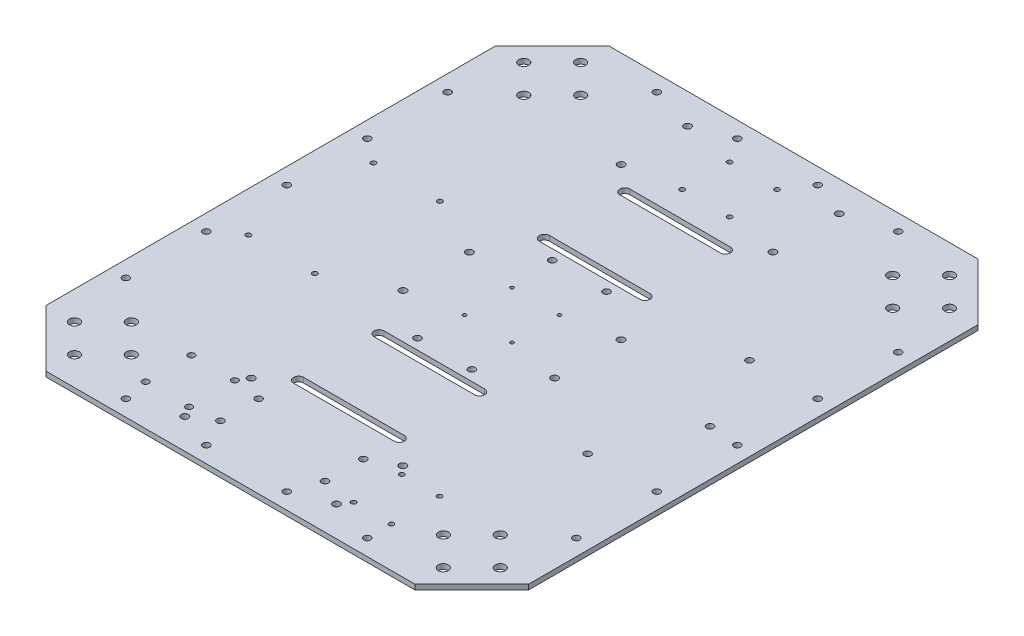
SolidWorks part; units mm, degrees
ref_plane "Front Plane" through (0, 0, 0) normal (0, 0, 1) x (1, 0, 0)
ref_plane "Top Plane" through (0, 0, 0) normal (0, 1, 0) x (1, 0, 0)
ref_plane "Right Plane" through (0, 0, 0) normal (1, 0, 0) x (0, 0, -1)
sketch "Sketch1" plane through (0, 0, 0) normal (0, 1, 0) x (1, 0, 0)
  line L0 (-121.2861, 87.138) -> (-85.365, 123.059)
  line L1 (-121.2861, 123.059) -> (183.5139, 123.059)
  line L2 (-121.2861, 123.059) -> (-121.2861, -232.541)
  line L3 (-121.2861, -232.541) -> (183.5139, -232.541)
  line L4 (183.5139, 123.059) -> (183.5139, -232.541)
  line L5 (31.1139, 95.069) -> (31.1139, -294.9418) construction
  line L6 (-146.0448, -54.741) -> (218.038, -54.741) construction
  line L7 (183.5139, 87.138) -> (147.5929, 123.059)
  line L8 (183.5139, -196.62) -> (147.5929, -232.541)
  line L9 (-121.2861, -196.62) -> (-85.365, -232.541)
  circle A0 centre (-16.7651, 104.009) radius 2.2225
  circle A1 centre (78.9929, 104.009) radius 2.2225
  circle A2 centre (-16.7651, 62.099) radius 2.2225
  circle A3 centre (78.9929, 62.099) radius 2.2225
  circle A4 centre (-16.7651, -171.581) radius 2.2225
  circle A5 centre (78.9929, -171.581) radius 2.2225
  circle A6 centre (78.9929, -213.491) radius 2.2225
  circle A7 centre (-16.7651, -213.491) radius 2.2225
  circle A8 centre (-16.7651, -33.786) radius 2.2225
  circle A9 centre (78.9929, -33.786) radius 2.2225
  circle A10 centre (78.9929, -75.696) radius 2.2225
  circle A11 centre (-16.7651, -75.696) radius 2.2225
  point P8 (31.1139, 123.059)
  point P11 (-121.2861, -54.741)
  dimension "D6" = 95.758
  dimension "D13" = 4.445
  dimension "D1" = 304.8
  dimension "D2" = 355.6
  dimension "D3" = 45
  dimension "D4" = 50.8
  dimension "D5" = 41.91
  dimension "D7" = 104.521
  dimension "D8" = 19.05
  dimension "D9" = 41.91
  dimension "D10" = 20.955
  dimension "D11" = 95.758
  dimension "D12" = 47.879
extrude "Boss-Extrude1" add sketch "Sketch1" along normal blind 3.175 contours L2 L9 L3 L8 L4 L7 L1 L0 region at (31.1139, 0, 54.741)
sketch "Sketch2" plane through (0, 3.175, 0) normal (0, 1, 0) x (1, 0, 0)
  line L0 (31.1139, 123.059) -> (31.1139, -287.8465) construction
  line L1 (-85.365, 123.059) -> (147.5929, 123.059) construction
  line L2 (183.5139, -54.741) -> (-158.2106, -54.741) construction
  line L3 (183.5139, 87.138) -> (183.5139, -196.62) construction
  circle A0 centre (13.8419, -12.069) radius 2.159
  circle A1 centre (48.1319, -12.069) radius 2.159
  circle A2 centre (13.8419, -97.159) radius 2.159
  circle A3 centre (48.1319, -97.159) radius 2.159
  dimension "D5" = 4.318
  dimension "D6" = 4.318
  dimension "D7" = 4.318
  dimension "D8" = 4.318
  dimension "D1" = 17.272
  dimension "D2" = 34.29
  dimension "D3" = 85.09
  dimension "D4" = 42.672
extrude "Cut-Extrude1" cut sketch "Sketch2" against normal through all
sketch "Sketch4" plane through (0, 3.175, 0) normal (0, 1, 0) x (1, 0, 0)
  line L0 (-0.6361, 48.256) -> (62.8639, 48.256) construction
  line L1 (-0.6361, 51.431) -> (62.8639, 51.431)
  line L2 (-0.6361, 45.081) -> (62.8639, 45.081)
  line L3 (-0.6361, -2.544) -> (62.8639, -2.544) construction
  line L4 (-0.6361, 0.631) -> (62.8639, 0.631)
  line L5 (-0.6361, -5.719) -> (62.8639, -5.719)
  line L6 (31.1139, 123.059) -> (31.1139, -75.2432) construction
  line L7 (-85.365, 123.059) -> (147.5929, 123.059) construction
  line L8 (-121.2861, -54.741) -> (257.7387, -54.741) construction
  line L9 (-121.2861, 87.138) -> (-121.2861, -196.62) construction
  line L10 (31.1139, -232.541) -> (31.1139, -34.2388) construction
  line L11 (-0.6361, -106.938) -> (62.8639, -106.938) construction
  line L12 (-0.6361, -110.113) -> (62.8639, -110.113)
  line L13 (-0.6361, -103.763) -> (62.8639, -103.763)
  line L14 (-0.6361, -157.738) -> (62.8639, -157.738) construction
  line L15 (-0.6361, -160.913) -> (62.8639, -160.913)
  line L16 (-0.6361, -154.563) -> (62.8639, -154.563)
  arc A0 (-0.6361, 51.431) -> (-0.6361, 45.081) centre (-0.6361, 48.256) ccw
  arc A1 (62.8639, 45.081) -> (62.8639, 51.431) centre (62.8639, 48.256) ccw
  arc A2 (-0.6361, 0.631) -> (-0.6361, -5.719) centre (-0.6361, -2.544) ccw
  arc A3 (62.8639, -5.719) -> (62.8639, 0.631) centre (62.8639, -2.544) ccw
  circle A4 centre (48.1319, -12.069) radius 2.159 construction
  arc A5 (-0.6361, -110.113) -> (-0.6361, -103.763) centre (-0.6361, -106.938) cw
  arc A6 (62.8639, -103.763) -> (62.8639, -110.113) centre (62.8639, -106.938) cw
  arc A7 (-0.6361, -160.913) -> (-0.6361, -154.563) centre (-0.6361, -157.738) cw
  arc A8 (62.8639, -154.563) -> (62.8639, -160.913) centre (62.8639, -157.738) cw
  point P2 (31.1139, 48.256)
  point P7 (31.1139, -2.544)
  point P28 (31.1139, -106.938)
  point P35 (31.1139, -157.738)
  dimension "D1" = 63.5
  dimension "D2" = 63.5
  dimension "D3" = 6.35
  dimension "D4" = 6.35
  dimension "D5" = 44.45
  dimension "D6" = 6.35
extrude "Cut-Extrude2" cut sketch "Sketch4" against normal through all
sketch "Sketch7" plane through (0, 3.175, 0) normal (0, 1, 0) x (1, 0, 0)
  line L0 (31.1139, 123.059) -> (31.1139, -19.2461) construction
  line L3 (-85.365, 123.059) -> (147.5929, 123.059) construction
  circle A0 centre (16.1279, 67.687) radius 1.524
  circle A1 centre (46.0999, 67.687) radius 1.524
  circle A2 centre (16.1279, 97.659) radius 1.524
  circle A3 centre (46.0999, 97.659) radius 1.524
  dimension "D1" = 3.048
  dimension "D2" = 3.048
  dimension "D4" = 14.986
  dimension "D3" = 29.972
  dimension "D5" = 25.4
extrude "Cut-Extrude3" cut sketch "Sketch7" against normal through all
sketch "Sketch8" plane through (0, 3.175, 0) normal (0, 1, 0) x (1, 0, 0)
  line L0 (-85.365, -232.541) -> (147.5929, -232.541) construction
  line L1 (183.5139, 87.138) -> (183.5139, -196.62) construction
  circle A0 centre (83.4379, -207.141) radius 1.524
  circle A1 centre (83.4379, -176.661) radius 1.524
  circle A2 centre (107.3139, -207.141) radius 1.524
  circle A3 centre (107.3139, -176.661) radius 1.524
  dimension "D1" = 3.048
  dimension "D2" = 30.48
  dimension "D3" = 23.876
  dimension "D4" = 25.4
  dimension "D5" = 76.2
extrude "Cut-Extrude4" cut sketch "Sketch8" against normal through all and the other way through all
sketch "Sketch9" plane through (0, 0, 0) normal (0, -1, 0) x (-1, 0, 0)
  line L0 (85.365, -232.541) -> (-147.5929, -232.541) construction
  line L1 (121.2861, 87.138) -> (121.2861, -196.62) construction
  circle A0 centre (48.1341, -206.887) radius 2.032
  circle A1 centre (20.7021, -206.887) radius 2.032
  circle A2 centre (48.1341, -177.931) radius 2.032
  circle A3 centre (20.7021, -177.931) radius 2.032
  dimension "D1" = 4.064
  dimension "D2" = 27.432
  dimension "D3" = 28.956
  dimension "D4" = 25.654
  dimension "D5" = 73.152
extrude "Cut-Extrude5" cut sketch "Sketch9" against normal through all
sketch "Sketch10" plane through (0, 0, 0) normal (0, -1, 0) x (1, 0, 0)
  line L0 (-85.365, 232.541) -> (147.5929, 232.541) construction
  line L1 (183.5139, -87.138) -> (183.5139, 196.62) construction
  circle A0 centre (-3.1761, 204.601) radius 2.159
  circle A1 centre (62.8639, 204.601) radius 2.159
  circle A2 centre (-3.1761, 180.471) radius 2.159
  circle A3 centre (62.8639, 180.471) radius 2.159
  dimension "D1" = 4.318
  dimension "D2" = 66.04
  dimension "D4" = 27.94
  dimension "D6" = 4.318
  dimension "D7" = 4.318
  dimension "D8" = 4.318
  dimension "D3" = 24.13
  dimension "D5" = 120.65
extrude "Cut-Extrude6" cut sketch "Sketch10" against normal through all
sketch "Sketch12" plane through (0, 0, 0) normal (0, -1, 0) x (1, 0, 0)
  line L0 (-121.2861, 54.741) -> (204.2138, 54.741) construction
  line L1 (-121.2861, -87.138) -> (-121.2861, 196.62) construction
  circle A0 centre (-95.8861, 94.216) radius 1.575
  circle A1 centre (-95.8861, 15.266) radius 1.575
  circle A2 centre (-53.9361, 15.266) radius 1.575
  circle A3 centre (-53.9361, 94.216) radius 1.575
  dimension "D1" = 3.15
  dimension "D2" = 3.15
  dimension "D3" = 3.15
  dimension "D4" = 3.15
  dimension "D5" = 78.95
  dimension "D6" = 39.475
  dimension "D7" = 41.95
  dimension "D8" = 25.4
extrude "Cut-Extrude7" cut sketch "Sketch12" against normal through all
sketch "Sketch13" plane through (0, 0, 0) normal (0, -1, 0) x (1, 0, 0)
  line L0 (31.1139, -123.059) -> (31.1139, 261.4711) construction
  line L1 (-85.365, -123.059) -> (147.5929, -123.059) construction
  line L2 (-121.2861, 54.741) -> (239.2508, 54.741) construction
  line L3 (-121.2861, -87.138) -> (-121.2861, 196.62) construction
  circle A0 centre (16.1139, 69.741) radius 1.1
  circle A1 centre (16.1139, 39.741) radius 1.1
  circle A2 centre (46.1139, 39.741) radius 1.1
  circle A3 centre (46.1139, 69.741) radius 1.1
  dimension "D1" = 2.2
  dimension "D2" = 2.2
  dimension "D3" = 30
  dimension "D4" = 15
  dimension "D5" = 15
extrude "Cut-Extrude8" cut sketch "Sketch13" against normal through all
sketch "Sketch14" plane through (0, 0, 0) normal (0, -1, 0) x (1, 0, 0)
  line L0 (31.1139, 232.541) -> (31.1139, -154.5354) construction
  line L1 (-85.365, 232.541) -> (147.5929, 232.541) construction
  line L2 (-121.2861, 54.741) -> (331.9066, 54.741) construction
  line L3 (-121.2861, -87.138) -> (-121.2861, 196.62) construction
  line L4 (-85.365, 214.5805) -> (-103.3255, 196.62) construction
  line L5 (-103.3255, 196.62) -> (-85.365, 178.6595) construction
  line L6 (-85.365, 178.6595) -> (-67.4045, 196.62) construction
  line L7 (-67.4045, 196.62) -> (-85.365, 214.5805) construction
  line L8 (-121.2861, 196.62) -> (-85.365, 232.541) construction
  line L9 (-103.3255, 214.5805) -> (-48.3665, 159.6215) construction
  circle A0 centre (-103.3255, 196.62) radius 3.175
  circle A1 centre (-85.365, 214.5805) radius 3.175
  circle A2 centre (-85.365, 178.6595) radius 3.175
  circle A3 centre (-67.4045, 196.62) radius 3.175
  circle A4 centre (129.6324, 196.62) radius 3.175
  circle A5 centre (147.5929, 178.6595) radius 3.175
  circle A6 centre (165.5534, 196.62) radius 3.175
  circle A7 centre (147.5929, 214.5805) radius 3.175
  circle A8 centre (-85.365, -105.0985) radius 3.175
  circle A9 centre (-103.3255, -87.138) radius 3.175
  circle A10 centre (-85.365, -69.1774) radius 3.175
  circle A11 centre (-67.4045, -87.138) radius 3.175
  circle A12 centre (165.5534, -87.138) radius 3.175
  circle A13 centre (147.5929, -69.1774) radius 3.175
  circle A14 centre (147.5929, -105.0985) radius 3.175
  circle A15 centre (129.6324, -87.138) radius 3.175
  dimension "D3" = 6.35
  dimension "D4" = 6.35
  dimension "D5" = 6.35
  dimension "D6" = 6.35
  dimension "D2" = 12.7
  dimension "D7" = 90
  dimension "D8" = 25.4
  dimension "D9" = 25.4
  dimension "D10" = 12.7
  dimension "D11" = 90
extrude "Cut-Extrude9" cut sketch "Sketch14" against normal through all
sketch "Sketch15" plane through (0, 0, 0) normal (0, -1, 0) x (1, 0, 0)
  line L0 (31.1139, 232.541) -> (31.1139, 125.875) construction
  line L1 (-85.365, 232.541) -> (147.5929, 232.541) construction
  line L2 (-121.2861, 54.741) -> (75.4631, 54.741) construction
  line L3 (-121.2861, -87.138) -> (-121.2861, 196.62) construction
  circle A0 centre (5.7139, 222.381) radius 2.159
  circle A1 centre (-45.0861, 222.381) radius 2.159
  circle A2 centre (-111.1261, 54.741) radius 2.159
  circle A3 centre (-111.1261, 105.541) radius 2.159
  circle A4 centre (-111.1261, 156.341) radius 2.159
  circle A5 centre (173.3539, 156.341) radius 2.159
  circle A6 centre (173.3539, 105.541) radius 2.159
  circle A7 centre (173.3539, 54.741) radius 2.159
  circle A8 centre (107.3139, 222.381) radius 2.159
  circle A9 centre (56.5139, 222.381) radius 2.159
  circle A10 centre (56.5139, -112.899) radius 2.159
  circle A11 centre (107.3139, -112.899) radius 2.159
  circle A12 centre (173.3539, 3.941) radius 2.159
  circle A13 centre (173.3539, -46.859) radius 2.159
  circle A14 centre (-111.1261, -46.859) radius 2.159
  circle A15 centre (-111.1261, 3.941) radius 2.159
  circle A16 centre (-45.0861, -112.899) radius 2.159
  circle A17 centre (5.7139, -112.899) radius 2.159
  dimension "D3" = 4.318
  dimension "D4" = 4.318
  dimension "D8" = 4.318
  dimension "D9" = 4.318
  dimension "D10" = 4.318
  dimension "D1" = 25.4
  dimension "D2" = 50.8
  dimension "D5" = 10.16
  dimension "D6" = 50.8
  dimension "D7" = 50.8
  dimension "D11" = 10.16
extrude "Cut-Extrude10" cut sketch "Sketch15" against normal through all
sketch "Sketch16" plane through (0, 0, 0) normal (0, -1, 0) x (-1, 0, 0)
  line L1 (-97.5856, -99.6794) -> (-147.4656, -99.6794)
  line L2 (-97.5856, -99.6794) -> (-97.5856, -11.5294)
  line L3 (-97.5856, -11.5294) -> (-147.4656, -11.5294)
  line L4 (-147.4656, -99.6794) -> (-147.4656, -11.5294)
  circle A0 centre (-130.8656, -106.6794) radius 2.159
  circle A1 centre (-130.8656, -4.5294) radius 2.159
  circle A2 centre (-154.4656, -53.0294) radius 2.159
  point P16 (0, 0)
  dimension "D3" = 7
  dimension "D4" = 7
  dimension "D5" = 7
  dimension "D6" = 16.6
  dimension "D7" = 16.6
  dimension "D8" = 46.65
  dimension "D9" = 4.318
  dimension "D10" = 4.318
  dimension "D11" = 4.318
  dimension "D1" = 88.15
  dimension "D2" = 49.88
extrude "Cut-Extrude11" cut sketch "Sketch16" against normal through all contours A2 | A0 | A1
